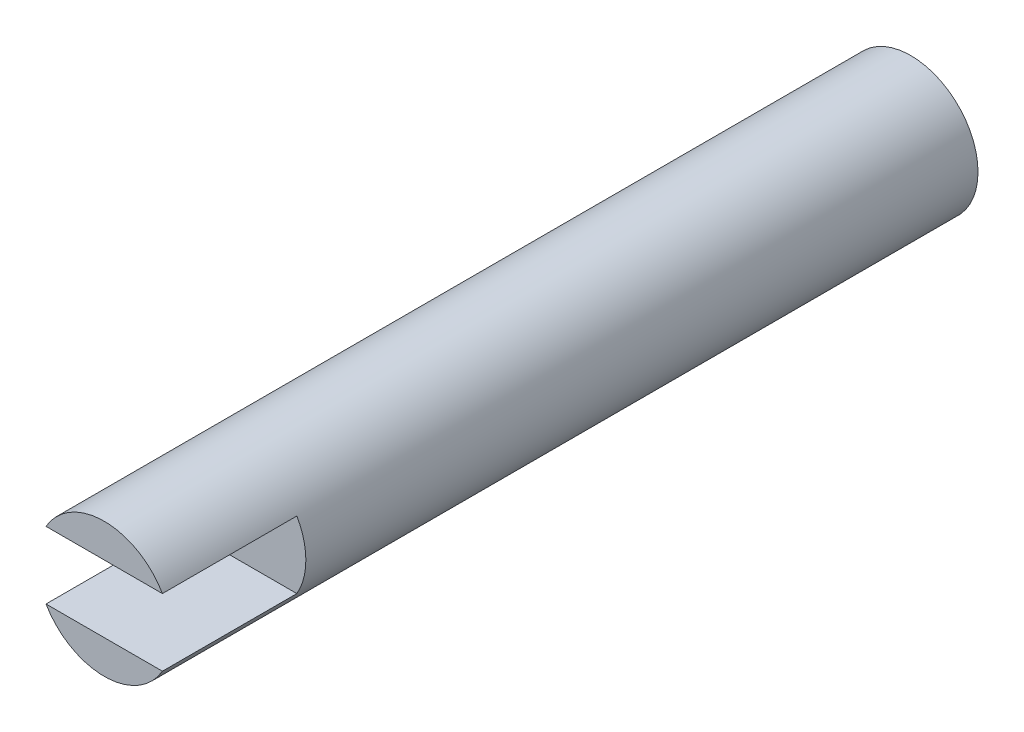
SolidWorks part; units mm, degrees
ref_plane "Front Plane" through (0, 0, 0) normal (0, 0, 1) x (1, 0, 0)
ref_plane "Top Plane" through (0, 0, 0) normal (0, 1, 0) x (1, 0, 0)
ref_plane "Right Plane" through (0, 0, 0) normal (1, 0, 0) x (0, 0, -1)
sketch "Sketch1" plane through (0, 0, 0) normal (0, 0, 1) x (1, 0, 0)
  circle A0 centre (0, 0) radius 25.4
  dimension "D1" = 50.8
extrude "Boss-Extrude1" add sketch "Sketch1" along normal blind 25.4 and the other way blind 279.4
sketch "Sketch3" plane through (0, 0, 0) normal (1, 0, 0) x (0, 0, -1)
  line L0 (-25.4, 25.4) -> (-25.4, -25.4) construction
  line L1 (-25.4, -12.7) -> (25.4, -12.7)
  line L2 (-25.4, -12.7) -> (-25.4, 12.7)
  line L3 (-25.4, 12.7) -> (25.4, 12.7)
  line L4 (25.4, -12.7) -> (25.4, 12.7)
  line L5 (-25.4, -25.4) -> (279.4, -25.4) construction
  dimension "D1" = 50.8
  dimension "D2" = 25.4
  dimension "D3" = 12.7
extrude "Cut-Extrude2" cut sketch "Sketch3" against normal through all both and the other way through all
